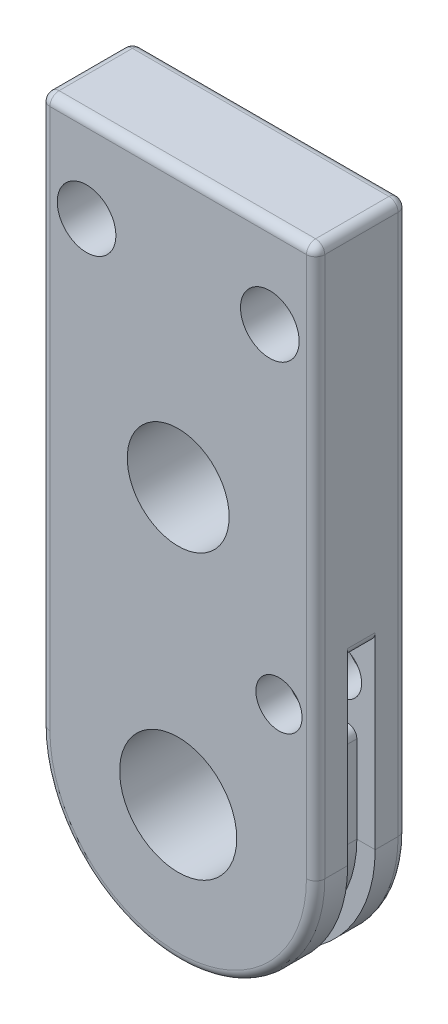
SolidWorks part; units mm, degrees
ref_plane "Front Plane" through (0, 0, 0) normal (0, 0, 1) x (1, 0, 0)
ref_plane "Top Plane" through (0, 0, 0) normal (0, 1, 0) x (1, 0, 0)
ref_plane "Right Plane" through (0, 0, 0) normal (1, 0, 0) x (0, 0, -1)
sketch "Sketch1" plane through (0, 0, 0) normal (0, 0, 1) x (1, 0, 0)
  line L0 (0, 0) -> (0, 19.05) construction
  line L3 (9.525, 38.1) -> (9.525, 0)
  line L7 (-9.525, 0) -> (-9.525, 38.1)
  line L8 (-9.525, 38.1) -> (9.525, 38.1)
  line L9 (-9.525, 32.004) -> (9.525, 32.004) construction
  line L11 (6.35, 32.004) -> (-6.35, 32.004)
  line L12 (6.985, 12.3952) -> (9.525, 12.3952)
  line L13 (6.985, 6.6548) -> (9.525, 6.6548)
  circle A0 centre (0, 0) radius 4.0577
  arc A1 (9.525, 0) -> (-9.525, 0) centre (0, 0) cw
  circle A2 centre (0, 19.05) radius 3.5306
  circle A4 centre (0, 0) radius 9.525 construction
  circle A5 centre (-6.35, 32.004) radius 2.032
  circle A6 centre (6.35, 32.004) radius 2.032
  circle A7 centre (6.985, 9.525) radius 1.6002
  arc A9 (6.985, 12.3952) -> (6.985, 6.6548) centre (6.985, 9.525) ccw
  point P11 (0, 32.004)
  point P17 (0, 9.525)
  dimension "D1" = 9.525
  dimension "D2" = 19.05
  dimension "D3" = 7.0612
  dimension "D4" = 8.1153
  dimension "D5" = 19.05
  dimension "D6" = 180
  dimension "D13" = 1.27
  dimension "D9" = 4.064
  dimension "D10" = 4.064
  dimension "D11" = 3.2004
  dimension "D7" = 6.096
  dimension "D8" = 3.175
  dimension "D12" = 2.54
  dimension "D15" = 19.05
extrude "Boss-Extrude1" add sketch "Sketch1" along normal mid plane 6.35 contours A9 L12 L3 L8 L7 A1 L13 A6 A5 A2 A0 | L12 A9 L13 L3 A7 region at (9.0121, 25.2476, 0) region at (9.4461, 9.525, 0)
extrude "Cut-Extrude4" cut sketch "Sketch1<7>" against normal mid plane 1.905 contours L12 A9 L13 L3 A7 region at (9.4461, 9.525, 0)
sketch "Sketch1<7>" plane through (0, 0, 0) normal (0, 0, 1) x (1, 0, 0) same geometry as "Sketch1"
sketch "Sketch3" plane through (0, 6.6548, 0) normal (0, 1, 0) x (1, 0, 0)
  line L0 (6.985, -0.9525) -> (9.525, -0.9525) construction
  line L1 (9.525, 0.9525) -> (8.255, 0.9525)
  line L2 (9.525, 0.9525) -> (9.525, -0.9525)
  line L3 (9.525, -0.9525) -> (8.255, -0.9525)
  line L4 (8.255, 0.9525) -> (8.255, -0.9525)
  dimension "D1" = 1.27
sketch "Sketch2" plane through (0, 0, 3.175) normal (0, 0, 1) x (1, 0, 0)
  line L0 (9.525, 6.6548) -> (9.525, 0)
  line L1 (9.525, 38.1) -> (9.525, 0) construction
  line L2 (-9.525, 0) -> (-9.525, 6.35)
  line L3 (-9.525, 0) -> (-9.525, 38.1) construction
  arc A0 (-9.525, 0) -> (9.525, 0) centre (0, 0) ccw construction
  arc A1 (-9.525, 0) -> (9.525, 0) centre (0, 0) ccw
  dimension "D1" = 6.35
sweep "Cut-Sweep1" cut profiles "Sketch3" path "Sketch2"
fillet "Fillet1" radius 0.635 10 edges at (-9.525, 19.05, -3.175) (0, -9.525, -3.175) (9.525, 38.1, 0) (0, 38.1, 3.175) (-9.525, 38.1, 0) (0, 38.1, -3.175) (9.525, 19.05, -3.175) (0, -9.525, 3.175) (-9.525, 19.05, 3.175) (9.525, 19.05, 3.175)
fillet "Fillet2" radius 0.635 4 edges at (8.255, 6.6548, 0) (9.525, 12.3952, 0) (-9.525, 6.35, 0) (-8.255, 6.35, 0)
